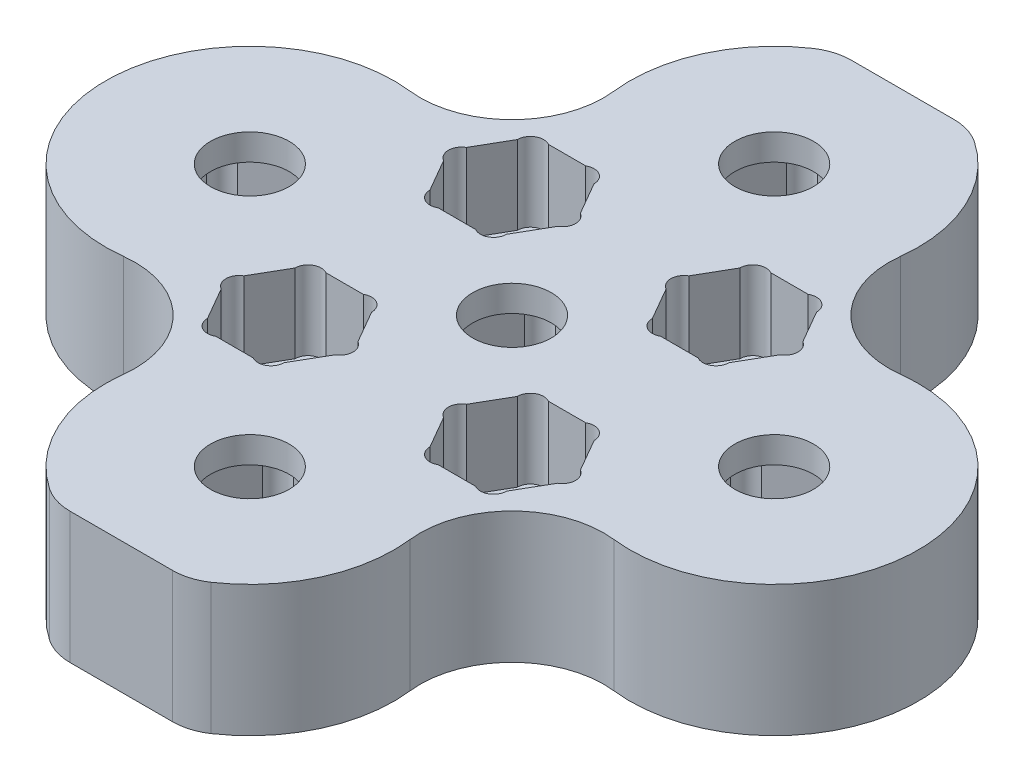
SolidWorks part; units mm, degrees
material "6061-T6 (SS)"
ref_plane "前视基准面" through (0, 0, 0) normal (0, 0, 1) x (1, 0, 0)
ref_plane "上视基准面" through (0, 0, 0) normal (0, 1, 0) x (1, 0, 0)
ref_plane "右视基准面" through (0, 0, 0) normal (1, 0, 0) x (0, 0, -1)
sketch "草图1" plane through (0, 0, 0) normal (0, 1, 0) x (1, 0, 0)
  line L0 (0, 10) -> (0, -10) construction
  line L1 (1.5877, 2.75) -> (-1.5877, 2.75)
  line L2 (-1.5877, 2.75) -> (-3.1754, 0)
  line L3 (-3.1754, 0) -> (-1.5877, -2.75)
  line L4 (-1.5877, -2.75) -> (1.5877, -2.75)
  line L5 (1.5877, -2.75) -> (3.1754, 0)
  line L6 (3.1754, 0) -> (1.5877, 2.75)
  line L7 (12.75, -1.5877) -> (12.75, 1.5877)
  line L8 (1.5877, 7.25) -> (3.1754, 10)
  line L9 (3.1754, 10) -> (1.5877, 12.75)
  line L10 (1.5877, 12.75) -> (-1.5877, 12.75)
  line L11 (-1.5877, 12.75) -> (-3.1754, 10)
  line L12 (-3.1754, 10) -> (-1.5877, 7.25)
  line L13 (-1.5877, 7.25) -> (1.5877, 7.25)
  line L14 (7.25, -1.5877) -> (10, -3.1754)
  line L15 (10, -3.1754) -> (12.75, -1.5877)
  line L16 (12.75, 1.5877) -> (10, 3.1754)
  line L17 (10, 3.1754) -> (7.25, 1.5877)
  line L18 (7.25, 1.5877) -> (7.25, -1.5877)
  line L19 (-1.5877, -12.75) -> (1.5877, -12.75)
  line L20 (-1.5877, -7.25) -> (-3.1754, -10)
  line L21 (-3.1754, -10) -> (-1.5877, -12.75)
  line L22 (1.5877, -12.75) -> (3.1754, -10)
  line L23 (3.1754, -10) -> (1.5877, -7.25)
  line L24 (1.5877, -7.25) -> (-1.5877, -7.25)
  line L25 (-12.75, 1.5877) -> (-12.75, -1.5877)
  line L26 (-7.25, 1.5877) -> (-10, 3.1754)
  line L27 (-10, 3.1754) -> (-12.75, 1.5877)
  line L28 (-12.75, -1.5877) -> (-10, -3.1754)
  line L29 (-10, -3.1754) -> (-7.25, -1.5877)
  line L30 (-7.25, -1.5877) -> (-7.25, 1.5877)
  circle A0 centre (0, 0) radius 2.75 construction
  circle A1 centre (0, 10) radius 2.75 construction
  arc A2 (5.4615, 9.3504) -> (-5.4615, 9.3504) centre (0, 10) ccw
  arc A3 (9.3504, -5.4615) -> (9.3504, 5.4615) centre (10, 0) ccw
  arc A4 (-5.4615, -9.3504) -> (5.4615, -9.3504) centre (0, -10) ccw
  arc A5 (-9.3504, 5.4615) -> (-9.3504, -5.4615) centre (-10, 0) ccw
  arc A6 (5.4615, 9.3504) -> (9.3504, 5.4615) centre (8.937, 8.937) ccw
  arc A7 (9.3504, -5.4615) -> (5.4615, -9.3504) centre (8.937, -8.937) ccw
  arc A8 (-5.4615, -9.3504) -> (-9.3504, -5.4615) centre (-8.937, -8.937) ccw
  arc A9 (-9.3504, 5.4615) -> (-5.4615, 9.3504) centre (-8.937, 8.937) ccw
  point P12 (0, 0)
  point P40 (0, 0)
  point P56 (0, 0)
  dimension "D5" = 11
  dimension "D6" = 7
  dimension "D1" = 5.5
  dimension "D2" = 4
  dimension "D3" = 20
  dimension "D4" = 4
extrude "凸台-拉伸1" add sketch "草图1" along normal blind 4
sketch "草图2" plane through (0, 4, 0) normal (0, 1, 0) x (1, 0, 0)
  line L0 (0, 0) -> (-4.2426, 4.2426) construction
  line L1 (0, 0) -> (-15.5, 0) construction
  circle A0 centre (-4.2426, 4.2426) radius 1
  circle A1 centre (4.2426, 4.2426) radius 1
  circle A2 centre (4.2426, -4.2426) radius 1
  circle A3 centre (-4.2426, -4.2426) radius 1
  arc A4 (-9.3504, 5.4615) -> (-9.3504, -5.4615) centre (-10, 0) ccw construction
  point P13 (0, 0)
  dimension "D1" = 2
  dimension "D3" = 45
  dimension "D4" = 12
  dimension "D2" = 4
extrude "切除-拉伸1" cut sketch "草图2" against normal through all
sketch "草图3" plane through (0, 4, 0) normal (0, 1, 0) x (1, 0, 0)
  circle A0 centre (-4.2426, -4.2426) radius 1 construction
  circle A1 centre (4.2426, -4.2426) radius 1 construction
  circle A2 centre (4.2426, 4.2426) radius 1 construction
  circle A3 centre (-4.2426, 4.2426) radius 1 construction
  circle A4 centre (-4.2426, -4.2426) radius 1
  circle A5 centre (4.2426, -4.2426) radius 1
  circle A6 centre (4.2426, 4.2426) radius 1
  circle A7 centre (-4.2426, 4.2426) radius 1
  arc A8 (9.3504, -5.4615) -> (5.4615, -9.3504) centre (8.937, -8.937) ccw
  arc A9 (9.3504, -5.4615) -> (9.3504, 5.4615) centre (10, 0) ccw
  arc A10 (5.4615, 9.3504) -> (9.3504, 5.4615) centre (8.937, 8.937) ccw
  arc A11 (5.4615, 9.3504) -> (-5.4615, 9.3504) centre (0, 10) ccw
  arc A12 (-9.3504, 5.4615) -> (-5.4615, 9.3504) centre (-8.937, 8.937) ccw
  arc A13 (-9.3504, 5.4615) -> (-9.3504, -5.4615) centre (-10, 0) ccw
  arc A14 (-5.4615, -9.3504) -> (-9.3504, -5.4615) centre (-8.937, -8.937) ccw
  arc A15 (-5.4615, -9.3504) -> (5.4615, -9.3504) centre (0, -10) ccw
  arc A16 (9.3504, -5.4615) -> (5.4615, -9.3504) centre (8.937, -8.937) ccw
  arc A17 (9.3504, -5.4615) -> (9.3504, 5.4615) centre (10, 0) ccw
  arc A18 (5.4615, 9.3504) -> (9.3504, 5.4615) centre (8.937, 8.937) ccw
  arc A19 (5.4615, 9.3504) -> (-5.4615, 9.3504) centre (0, 10) ccw
  arc A20 (-9.3504, 5.4615) -> (-5.4615, 9.3504) centre (-8.937, 8.937) ccw
  arc A21 (-9.3504, 5.4615) -> (-9.3504, -5.4615) centre (-10, 0) ccw
  arc A22 (-5.4615, -9.3504) -> (-9.3504, -5.4615) centre (-8.937, -8.937) ccw
  arc A23 (-5.4615, -9.3504) -> (5.4615, -9.3504) centre (0, -10) ccw
  circle A24 centre (0, 10) radius 1.5
  circle A25 centre (10, 0) radius 1.5
  circle A26 centre (0, -10) radius 1.5
  circle A27 centre (-10, 0) radius 1.5
  circle A28 centre (0, 0) radius 1.5
  dimension "D2" = 3
  dimension "D1" = 0
extrude "凸台-拉伸2" add sketch "草图3" along normal blind 1
sketch "草图5" plane through (0, 5, 0) normal (0, 1, 0) x (1, 0, 0)
  line L1 (-5.4551, 6.3426) -> (-6.6675, 4.2426)
  line L2 (-6.6675, 4.2426) -> (-5.4551, 2.1426)
  line L3 (-5.4551, 2.1426) -> (-3.0302, 2.1426)
  line L4 (-3.0302, 2.1426) -> (-1.8178, 4.2426)
  line L5 (-1.8178, 4.2426) -> (-3.0302, 6.3426)
  line L6 (-3.0302, 6.3426) -> (-5.4551, 6.3426)
  line L25 (3.0302, 2.1426) -> (5.4551, 2.1426)
  line L26 (5.4551, 2.1426) -> (6.6675, 4.2426)
  line L27 (6.6675, 4.2426) -> (5.4551, 6.3426)
  line L28 (5.4551, 6.3426) -> (3.0302, 6.3426)
  line L29 (3.0302, 6.3426) -> (1.8178, 4.2426)
  line L30 (1.8178, 4.2426) -> (3.0302, 2.1426)
  line L31 (3.0302, -2.1426) -> (1.8178, -4.2426)
  line L32 (1.8178, -4.2426) -> (3.0302, -6.3426)
  line L33 (3.0302, -6.3426) -> (5.4551, -6.3426)
  line L34 (5.4551, -6.3426) -> (6.6675, -4.2426)
  line L35 (6.6675, -4.2426) -> (5.4551, -2.1426)
  line L36 (5.4551, -2.1426) -> (3.0302, -2.1426)
  line L37 (-3.0302, -2.1426) -> (-5.4551, -2.1426)
  line L38 (-5.4551, -2.1426) -> (-6.6675, -4.2426)
  line L39 (-6.6675, -4.2426) -> (-5.4551, -6.3426)
  line L40 (-5.4551, -6.3426) -> (-3.0302, -6.3426)
  line L41 (-3.0302, -6.3426) -> (-1.8178, -4.2426)
  line L42 (-1.8178, -4.2426) -> (-3.0302, -2.1426)
  circle A0 centre (-4.2426, 4.2426) radius 2.1 construction
  circle A1 centre (4.2426, 4.2426) radius 2.1 construction
  circle A2 centre (4.2426, -4.2426) radius 2.1 construction
  circle A3 centre (-4.2426, -4.2426) radius 2.1 construction
  dimension "D1" = 4.2
extrude "切除-拉伸2" cut sketch "草图5" against normal blind 3
ref_plane "基准面1" through (-3.0302, 2, -6.3426) normal (0, 1, 0) x (1, 0, 0)
sketch "草图6" plane through (0, 0, 0) normal (0, -1, 0) x (1, 0, 0)
  line L1 (2.498, 14.9) -> (-2.498, 14.9)
  line L2 (2.498, 14.9) -> (2.498, -14.9) construction
  line L3 (2.498, -14.9) -> (-2.498, -14.9)
  line L4 (-2.498, 14.9) -> (-2.498, -14.9) construction
  line L5 (0, -14.9) -> (0, 14.9) construction
  line L6 (2.498, 0) -> (-2.498, 0) construction
  arc A0 (-5.4615, -9.3504) -> (5.4615, -9.3504) centre (0, -10) ccw construction
  arc A1 (5.4615, 9.3504) -> (-5.4615, 9.3504) centre (0, 10) ccw construction
  arc A2 (2.498, 14.9) -> (-2.498, 14.9) centre (0, 10) ccw
  arc A3 (-2.498, -14.9) -> (2.498, -14.9) centre (0, -10) ccw
  point P0 (0, 0)
  dimension "D1" = 29.8
extrude "切除-拉伸3" cut sketch "草图6" against normal blind 10
fillet "圆角1" radius 2 2 edges at (-2.498, 2.5, 14.9) (2.498, 2.5, -14.9)
fillet "圆角2" radius 0.5 6 edges at (5.4551, 3.5, 2.1426) (6.6675, 3.5, 4.2426) (3.0302, 3.5, 6.3426) (1.8178, 3.5, 4.2426) (3.0302, 3.5, 2.1426) (5.4551, 3.5, 6.3426)
sketch "草图7" plane through (0, 0, 0) normal (0, -1, 0) x (1, 0, 0)
  line L1 (12.75, -1.5877) -> (10, 0) construction
  line L2 (0, 2.75) -> (0, 7.25) construction
  line L3 (-1.5877, 2.75) -> (1.5877, 2.75) construction
  line L4 (1.5877, 7.25) -> (-1.5877, 7.25) construction
  line L5 (0, 5) -> (2.3973, 5) construction
  circle A5 centre (12.317, -1.3377) radius 0.5
  circle A6 centre (10, -2.6754) radius 0.5
  circle A7 centre (7.683, -1.3377) radius 0.5
  circle A8 centre (7.683, 1.3377) radius 0.5
  circle A9 centre (10, 2.6754) radius 0.5
  circle A10 centre (12.317, 1.3377) radius 0.5
  circle A11 centre (-1.3377, -12.317) radius 0.5
  circle A12 centre (-2.6754, -10) radius 0.5
  circle A13 centre (-1.3377, -7.683) radius 0.5
  circle A14 centre (1.3377, -7.683) radius 0.5
  circle A15 centre (2.6754, -10) radius 0.5
  circle A16 centre (1.3377, -12.317) radius 0.5
  circle A17 centre (-12.317, 1.3377) radius 0.5
  circle A18 centre (-10, 2.6754) radius 0.5
  circle A19 centre (-7.683, 1.3377) radius 0.5
  circle A20 centre (-7.683, -1.3377) radius 0.5
  circle A21 centre (-10, -2.6754) radius 0.5
  circle A22 centre (-12.317, -1.3377) radius 0.5
  circle A23 centre (1.3377, 12.317) radius 0.5
  circle A24 centre (2.6754, 10) radius 0.5
  circle A25 centre (1.3377, 7.683) radius 0.5
  circle A26 centre (-1.3377, 7.683) radius 0.5
  circle A27 centre (-2.6754, 10) radius 0.5
  circle A28 centre (-1.3377, 12.317) radius 0.5
  circle A30 centre (-1.3377, -2.317) radius 0.5
  circle A31 centre (-2.6754, 0) radius 0.5
  circle A32 centre (-1.3377, 2.317) radius 0.5
  circle A33 centre (1.3377, 2.317) radius 0.5
  circle A34 centre (2.6754, 0) radius 0.5
  circle A35 centre (1.3377, -2.317) radius 0.5
  point P21 (10, 0)
  point P59 (0, 0)
  dimension "D1" = 1
  dimension "D2" = 6
  dimension "D3" = 4
extrude "切除-拉伸4" cut sketch "草图7" against normal up to surface (4 mm away) up to face at (10, 4, 0)
sketch "草图8" plane through (0, 5, 0) normal (0, 1, 0) x (1, 0, 0)
  line L0 (6.6675, 4.2426) -> (4.2426, 4.2426) construction
  line L1 (0, 0) -> (0, 10) construction
  line L2 (0, 0) -> (10.0067, 0) construction
  circle A0 centre (6.1675, 4.2426) radius 0.5
  circle A1 centre (5.2051, 2.5757) radius 0.5
  circle A2 centre (3.2802, 2.5757) radius 0.5
  circle A3 centre (2.3178, 4.2426) radius 0.5
  circle A4 centre (3.2802, 5.9096) radius 0.5
  circle A5 centre (5.2051, 5.9096) radius 0.5
  circle A12 centre (5.2051, -5.9096) radius 0.5
  circle A13 centre (3.2802, -5.9096) radius 0.5
  circle A14 centre (2.3178, -4.2426) radius 0.5
  circle A15 centre (3.2802, -2.5757) radius 0.5
  circle A16 centre (5.2051, -2.5757) radius 0.5
  circle A17 centre (6.1675, -4.2426) radius 0.5
  circle A18 centre (-6.1675, -4.2426) radius 0.5
  circle A19 centre (-5.2051, -2.5757) radius 0.5
  circle A20 centre (-3.2802, -2.5757) radius 0.5
  circle A21 centre (-2.3178, -4.2426) radius 0.5
  circle A22 centre (-3.2802, -5.9096) radius 0.5
  circle A23 centre (-5.2051, -5.9096) radius 0.5
  circle A24 centre (-5.2051, 5.9096) radius 0.5
  circle A25 centre (-3.2802, 5.9096) radius 0.5
  circle A26 centre (-2.3178, 4.2426) radius 0.5
  circle A27 centre (-3.2802, 2.5757) radius 0.5
  circle A28 centre (-5.2051, 2.5757) radius 0.5
  circle A29 centre (-6.1675, 4.2426) radius 0.5
  point P19 (4.2426, 4.2426)
  point P56 (0, 0)
  dimension "D1" = 1
  dimension "D2" = 6
extrude "切除-拉伸5" cut sketch "草图8" against normal up to surface (3 mm away) up to face at (4.2426, 2, -4.2426)
